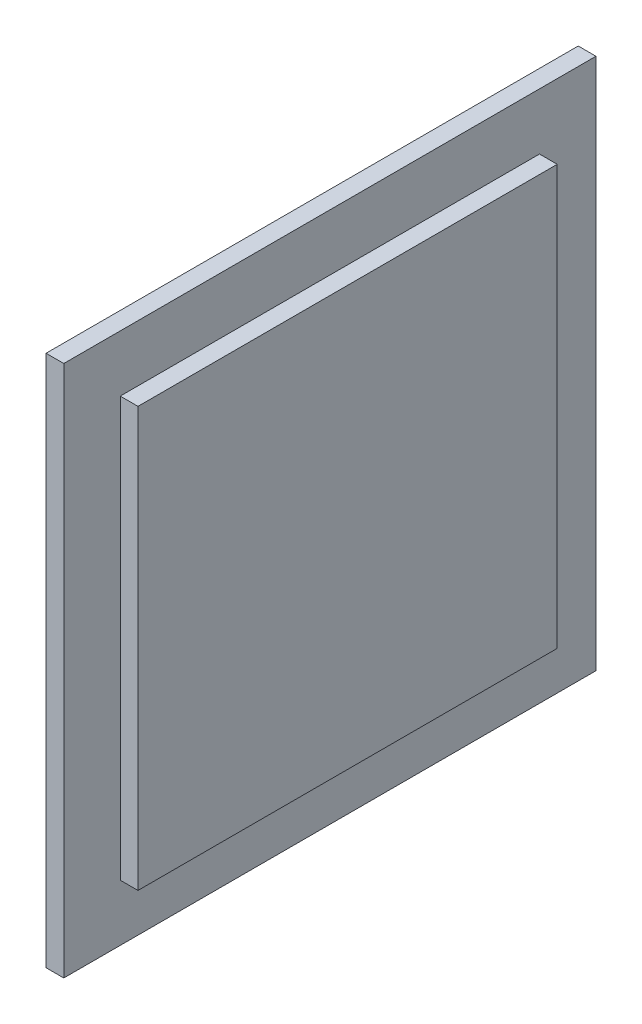
SolidWorks part; units mm, degrees
material "6061 Alloy"
ref_plane "Front Plane" through (0, 0, 0) normal (0, 0, 1) x (1, 0, 0)
ref_plane "Top Plane" through (0, 0, 0) normal (0, 1, 0) x (1, 0, 0)
ref_plane "Right Plane" through (0, 0, 0) normal (1, 0, 0) x (0, 0, -1)
sketch "Sketch1" plane through (0, 0, 0) normal (1, 0, 0) x (0, 0, -1)
  line L1 (0, 0) -> (228.6, 0)
  line L2 (0, 0) -> (0, -228.6)
  line L3 (0, -228.6) -> (228.6, -228.6)
  line L4 (228.6, 0) -> (228.6, -228.6)
  line L5 (24.257, -24.257) -> (204.343, -24.257)
  line L6 (24.257, -24.257) -> (24.257, -204.343)
  line L7 (24.257, -204.343) -> (204.343, -204.343)
  line L8 (204.343, -24.257) -> (204.343, -204.343)
  point P9 (114.3, 0)
  point P10 (114.3, -24.257)
  point P11 (228.6, -114.3)
  point P12 (204.343, -114.3)
  dimension "D1" = 228.6
  dimension "D2" = 180.086
extrude "Boss-Extrude1" add sketch "Sketch1" along normal blind 7.62 contours L8 L5 L6 L7 | L4 L1 L2 L3 L5 L8 L7 L6 region at (0, -3.2329, -114.3) region at (0, -114.3, -114.3)
extrude "Boss-Extrude2" add sketch "Sketch1<3>" along normal blind 7.62 from surface contours L8 L5 L6 L7 region at (0, -114.3, -114.3) starting at face at (7.62, -114.3, -114.3)
sketch "Sketch1<3>" plane through (0, 0, 0) normal (1, 0, 0) x (0, 0, -1) same geometry as "Sketch1"
